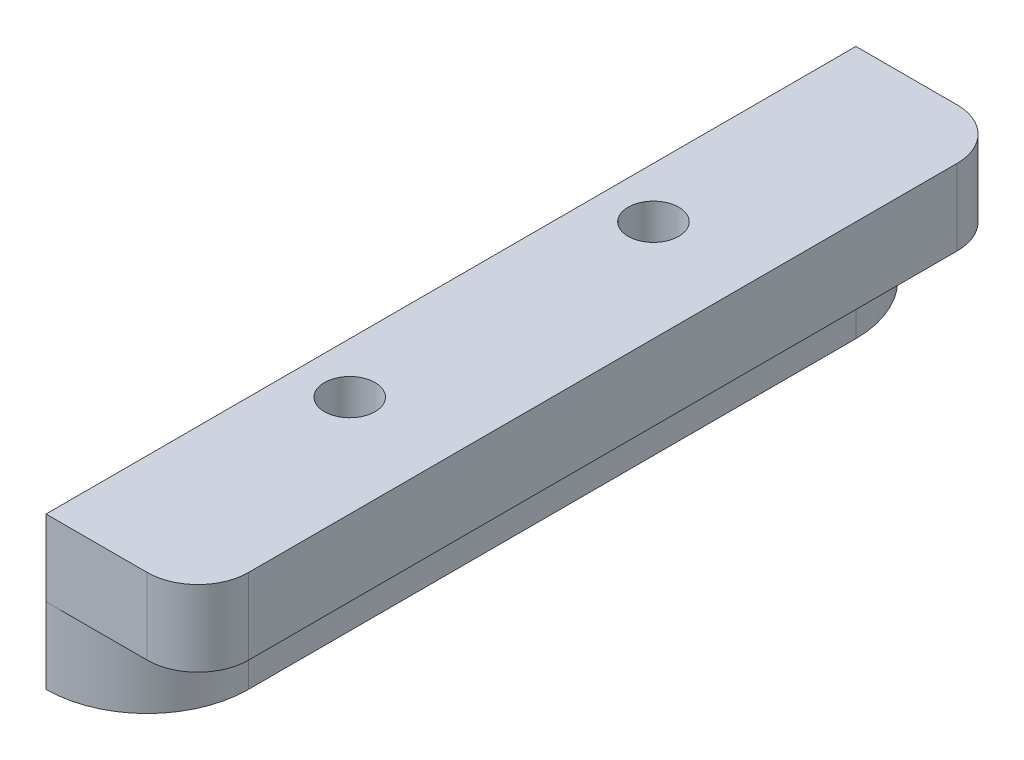
SolidWorks part; units mm, degrees
ref_plane "Front" through (0, 0, 0) normal (0, 0, 1) x (1, 0, 0)
ref_plane "Top" through (0, 0, 0) normal (0, 1, 0) x (1, 0, 0)
ref_plane "Right" through (0, 0, 0) normal (1, 0, 0) x (0, 0, -1)
sketch "Sketch1" plane through (0, 0, 0) normal (0, 1, 0) x (1, 0, 0)
  line L1 (-9.525, -50.8) -> (9.525, -50.8)
  line L2 (-9.525, -50.8) -> (-9.525, 50.8)
  line L3 (-9.525, 50.8) -> (9.525, 50.8)
  line L4 (9.525, -50.8) -> (9.525, 50.8)
  line L5 (-9.525, -50.8) -> (9.525, 50.8) construction
  line L6 (-9.525, 50.8) -> (9.525, -50.8) construction
  point P0 (0, 0)
  dimension "D1" = 101.6
  dimension "D2" = 19.05
extrude "Boss-Extrude1" add sketch "Sketch1" along normal mid plane 19.05 contours L4 L3 L2 L1
sketch "Sketch2" plane through (0, 0, 50.8) normal (0, 0, 1) x (1, 0, 0)
  line L0 (-9.525, 9.525) -> (9.525, 9.525) construction
  line L1 (3.175, 0) -> (9.525, 0)
  line L2 (3.175, 0) -> (3.175, -9.525)
  line L3 (3.175, -9.525) -> (9.525, -9.525)
  line L4 (9.525, 0) -> (9.525, -9.525)
  line L5 (3.175, 0) -> (9.525, -9.525) construction
  line L6 (3.175, -9.525) -> (9.525, 0) construction
  point P0 (6.35, -4.7625)
  dimension "D1" = 6.35
  dimension "D2" = 9.525
extrude "Cut-Extrude1" cut sketch "Sketch2" against normal through all
sketch "Sketch3" plane through (0, 9.525, 0) normal (0, 1, 0) x (1, 0, 0)
  line L0 (-3.175, 19.05) -> (-3.175, -19.05) construction
  line L1 (-50, 0) -> (50, 0) construction
  line L2 (-9.525, -50.8) -> (-9.525, 50.8) construction
  point P0 (-3.175, 19.05)
  point P1 (-3.175, -19.05)
  point P4 (-3.175, 0)
  dimension "D1" = 38.1
  dimension "D2" = 6.35
hole_wizard "1/4 (0.25) Diameter Hole1" positions "Sketch4" profile "Sketch6" hole size "1/4" standard "ANSI Inch"
sketch "Sketch4" plane through (0, 9.525, 0) normal (0, 1, 0) x (1, 0, 0)
  point P0 (-3.175, 19.05)
  point P3 (-3.175, -19.05)
sketch "Sketch6" plane through (-3.175, 9.525, -19.05) normal (1, 0, 0) x (0, 0, 1)
  line L0 (0, 0) -> (0, 27.3077)
  line L1 (0, 27.3077) -> (3.175, 25.4)
  line L2 (3.175, 25.4) -> (3.175, 0)
  line L5 (3.175, 0) -> (0, 0)
  line L10 (0, 27.3077) -> (-3.175, 25.4) construction
  line L11 (0, -6.35) -> (0, 107.95) construction
  dimension "Hole Dia." = 6.35
  dimension "Hole Depth" = 25.4
  dimension "Drill Angle" = 118
fillet "Fillet1" radius 12.7 2 edges at (3.175, -4.7625, -50.8) (3.175, -4.7625, 50.8)
fillet "Fillet2" radius 6.35 2 edges at (9.525, 4.7625, -50.8) (9.525, 4.7625, 50.8)
